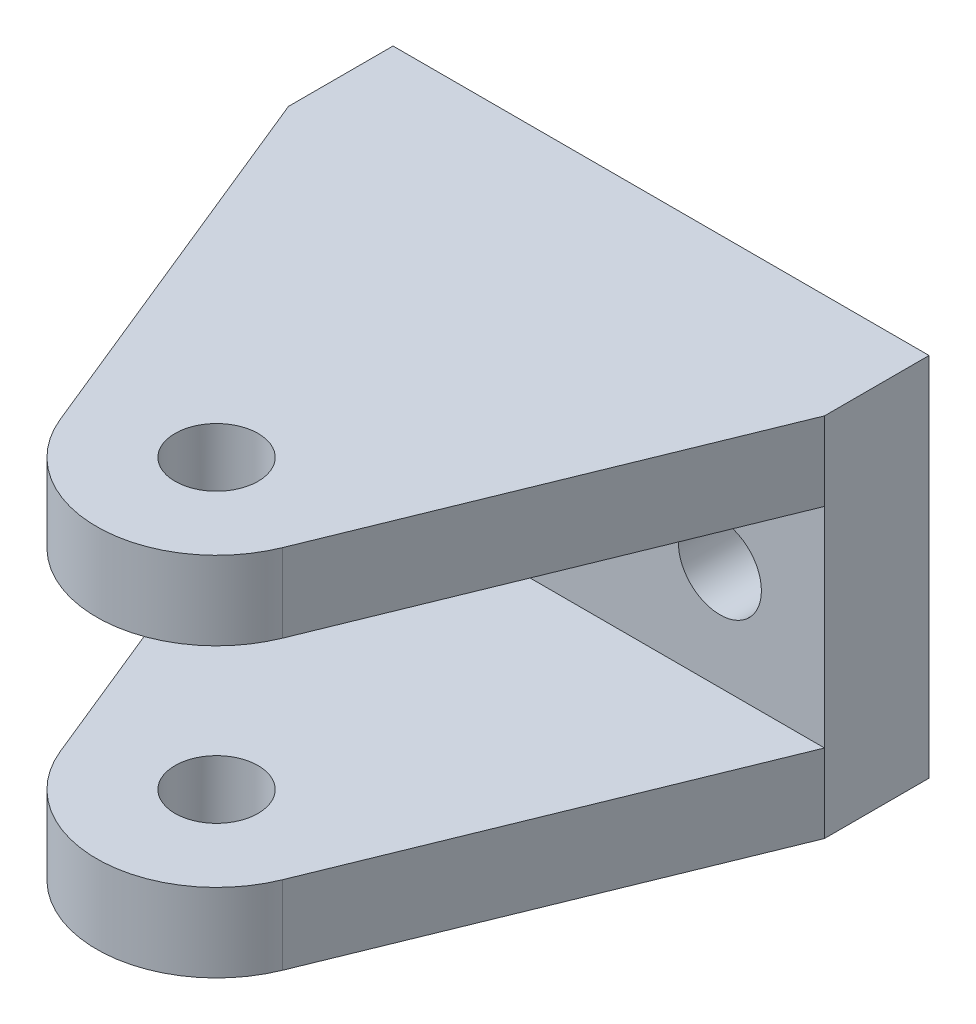
SolidWorks part; units mm, degrees
ref_plane "Front Plane" through (0, 0, 0) normal (0, 0, 1) x (1, 0, 0)
ref_plane "Top Plane" through (0, 0, 0) normal (0, 1, 0) x (1, 0, 0)
ref_plane "Right Plane" through (0, 0, 0) normal (1, 0, 0) x (0, 0, -1)
sketch "Sketch1" plane through (0, 0, 0) normal (0, 0, 1) x (1, 0, 0)
  line L0 (12.5, 0) -> (-12.5, 0) construction
  line L1 (-20.5, -14) -> (20.5, -14)
  line L2 (-20.5, -14) -> (-20.5, 14)
  line L3 (-20.5, 14) -> (20.5, 14)
  line L4 (20.5, -14) -> (20.5, 14)
  line L5 (-20.5, -14) -> (20.5, 14) construction
  line L6 (-20.5, 14) -> (20.5, -14) construction
  circle A0 centre (12.5, 0) radius 3.175
  circle A1 centre (-12.5, 0) radius 3.175
  point P0 (0, 0)
  point P10 (-9.7772, 5.968)
  point P11 (-4.615, 0.3271)
  point P12 (5.0123, 3.0595)
  point P13 (-12.2169, 6.6844)
  dimension "D1" = 6.35
  dimension "D2" = 25
  dimension "D3" = 8
  dimension "D4" = 14
extrude "Boss-Extrude1" add sketch "Sketch1" along normal blind 8
sketch "Sketch2" plane through (0, 0, 8) normal (0, 0, 1) x (1, 0, 0)
  line L0 (-12.5, 0) -> (12.5, 0) construction
  line L2 (-20.5, 8) -> (20.5, 8)
  line L3 (-20.5, 8) -> (-20.5, 14)
  line L4 (-20.5, 14) -> (20.5, 14)
  line L5 (20.5, 8) -> (20.5, 14)
  line L6 (-20.5, 8) -> (20.5, 14) construction
  line L7 (-20.5, 14) -> (20.5, 8) construction
  line L8 (-20.5, 14) -> (-20.5, -14) construction
  line L9 (20.5, -8) -> (20.5, -14)
  line L10 (-20.5, -8) -> (-20.5, -14)
  line L11 (-20.5, -14) -> (20.5, -8) construction
  line L12 (-20.5, -8) -> (20.5, -14) construction
  line L13 (-20.5, -8) -> (20.5, -8)
  line L14 (-20.5, -14) -> (20.5, -14)
  circle A0 centre (-12.5, 0) radius 3.175 construction
  circle A1 centre (12.5, 0) radius 3.175 construction
  point P6 (0, 11)
  point P11 (20.5, 14)
  point P13 (-20.5, 5.4759)
  point P16 (0, 6.3453)
  point P17 (0, 6.7784)
  point P18 (6.7197, 6.5828)
  point P21 (0, -11)
  dimension "D1" = 6
extrude "Boss-Extrude2" add sketch "Sketch2" along normal blind 53
sketch "Sketch3" plane through (0, 0, 0) normal (0, 1, 0) x (1, 0, 0)
  point P0 (0, -34)
  point P1 (0, 0)
  dimension "D1" = 34
ref_point "UBJ Point"
sketch "Sketch4" plane through (0, 0, 0) normal (0, 1, 0) x (1, 0, 0)
  circle A0 centre (0, -34) radius 3.175
  dimension "D1" = 6.35
extrude "Cut-Extrude1" cut sketch "Sketch4" against normal up to surface and the other way up to surface up to face at (0, -14, 30.5) other way up to face at (0, 14, 30.5)
sketch "Sketch5" plane through (0, 0, 0) normal (0, 1, 0) x (1, 0, 0)
  line L0 (20.5, -8) -> (8.4969, -37.4617)
  line L1 (-8.4969, -37.4617) -> (-20.5, -8)
  line L4 (20.5, 0) -> (-20.5, 0)
  line L5 (-20.5, 0) -> (-20.5, -61)
  line L6 (-20.5, -61) -> (20.5, -61)
  line L7 (20.5, -61) -> (20.5, 0)
  line L9 (-20.5, -8) -> (-20.5, -61)
  line L10 (-20.5, -61) -> (20.5, -61)
  line L11 (20.5, -61) -> (20.5, -8)
  line L12 (20.5, -8) -> (-20.5, -8)
  line L13 (20.5, -61) -> (20.5, -8)
  line L14 (-20.5, -61) -> (20.5, -61)
  line L15 (-20.5, -8) -> (-20.5, -61)
  line L17 (20.5, -61) -> (20.5, -8)
  line L18 (-20.5, -61) -> (20.5, -61)
  line L19 (-20.5, -8) -> (-20.5, -61)
  arc A0 (-8.4969, -37.4617) -> (8.4969, -37.4617) centre (0, -34) ccw
  circle A1 centre (0, -34) radius 3.175 construction
  circle A2 centre (0, -34) radius 3.175 construction
  point P7 (-4.5691, -41.5311)
  point P9 (10.2544, -37.5548)
  point P12 (11.9584, -37.4664)
  dimension "D3" = 6
  dimension "D1" = 0
  dimension "D2" = 0
extrude "Cut-Extrude2" cut sketch "Sketch5" against normal up to surface and the other way up to surface contours A0 L1 L9 L10 L11 L0 region at (0, 0, 43.6449) up to face at (0, -14, 37.175) other way up to face at (0, 14, 30.825)
